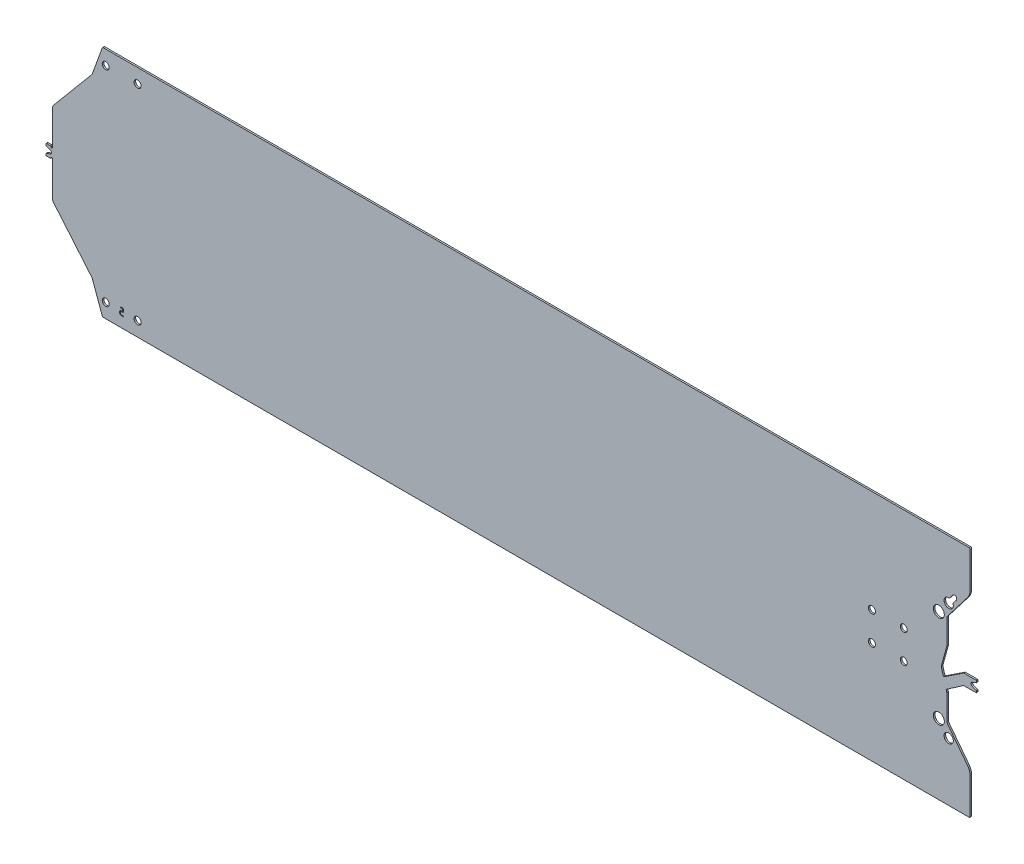
SolidWorks part; units mm, degrees
extrude "Base-Extrude" add sketch "Sketch1" along normal blind 5
sketch "Sketch1" plane through (0, 0, 0) normal (0, 0, 1) x (1, 0, 0)
  line L0 (0, 363.5) -> (0, 252.0782)
  line L1 (81.8142, 0) -> (-2880, 0) construction
  line L2 (-3, 366.5) -> (-2720.5358, 366.5)
  line L3 (-2754.7906, -278.1569) -> (-2723.3548, -364.5261)
  line L4 (-2756.5271, 275.1493) -> (-2875.3209, 133.5763)
  line L5 (-2880, 120.7206) -> (-2880, 0)
  line L6 (-2754.7906, 278.1569) -> (-2723.3548, 364.5261)
  line L7 (-2892.0623, 0) -> (-2897, 0)
  line L8 (-2900, -3) -> (-2900, -12.6577)
  line L9 (-2897.7276, -15.5681) -> (-2882.2724, -19.4319)
  line L10 (-2880, -1) -> (-2880, 0)
  line L11 (-2880, 90) -> (0, 90) construction
  line L12 (-2850.9687, 277.5) -> (0, 277.5) construction
  line L13 (-67, 90) -> (-67, 277.5) construction
  line L14 (-73, 63) -> (-89.7303, 2.6724)
  line L15 (-90.094, 0) -> (17, 0)
  line L16 (20, -3) -> (20, -17.4378)
  line L17 (-3, -366.5) -> (-2720.5358, -366.5)
  line L18 (-2880, -120.7206) -> (-2880, -22.3423)
  line L19 (0, -252.0782) -> (0, -363.5)
  line L20 (17.4693, -20.4008) -> (-80.5102, -35.9192)
  line L21 (-8.2659, 227.7277) -> (-70.9335, 146.0576)
  line L22 (-73, 139.97) -> (-73, 63)
  line L23 (-8.2659, -227.7277) -> (-70.9335, -146.0576)
  line L24 (-73, -63) -> (-73, -139.97)
  line L25 (-2756.5271, -275.1493) -> (-2875.3209, -133.5763)
  line L26 (-73, -63) -> (-80.5102, -35.9192)
  line L27 (-67, 183.75) -> (-48.7372, 207.5506) construction
  line L28 (-43.1837, 203.2893) -> (-52.7039, 190.8823)
  line L29 (-54.2906, 211.8119) -> (-63.8108, 199.405)
  circle A0 centre (-98, 145.25) radius 17.25
  arc A1 (-2723.3548, 364.5261) -> (-2720.5358, 366.5) centre (-2720.5358, 363.5) cw
  arc A2 (-2880, -120.7206) -> (-2875.3209, -133.5763) centre (-2860, -120.7206) ccw
  arc A3 (-2754.7906, -278.1569) -> (-2756.5271, -275.1493) centre (-2764.1876, -281.5771) ccw
  arc A4 (-2880, -1) -> (-2887.5832, -2.7778) centre (-2884, -1) cw
  arc A5 (-2887.5832, -2.7778) -> (-2892.0623, 0) centre (-2892.0623, -5) ccw
  arc A6 (-2723.3548, -364.5261) -> (-2720.5358, -366.5) centre (-2720.5358, -363.5) ccw
  arc A7 (-2754.7906, 278.1569) -> (-2756.5271, 275.1493) centre (-2764.1876, 281.5771) cw
  circle A8 centre (-2712.5, 321.5) radius 11
  circle A9 centre (-2612.5, 321.5) radius 11
  circle A10 centre (-2612.5, -321.5) radius 11
  circle A11 centre (-2712.5, -321.5) radius 11
  arc A12 (-43.1837, 203.2893) -> (-54.2906, 211.8119) centre (-48.7372, 207.5506) ccw
  arc A13 (-63.8108, 199.405) -> (-66.3296, 198.2345) centre (-66.1909, 201.2313) cw
  arc A14 (-2880, 120.7206) -> (-2875.3209, 133.5763) centre (-2860, 120.7206) cw
  arc A15 (0, 363.5) -> (-3, 366.5) centre (-3, 363.5) ccw
  arc A16 (0, 252.0782) -> (-8.2659, 227.7277) centre (-40, 252.0782) cw
  arc A17 (-73, 139.97) -> (-70.9335, 146.0576) centre (-63, 139.97) cw
  arc A18 (-52.7039, 190.8823) -> (-53.1826, 188.1464) centre (-50.3238, 189.0561) ccw
  arc A19 (-2900, -3) -> (-2897, 0) centre (-2897, -3) cw
  arc A20 (-2897.7276, -15.5681) -> (-2900, -12.6577) centre (-2897, -12.6577) cw
  arc A21 (-89.7303, 2.6724) -> (-90.094, 0) centre (-80.094, 0) ccw
  arc A22 (-73, -139.97) -> (-70.9335, -146.0576) centre (-63, -139.97) ccw
  arc A23 (0, -252.0782) -> (-8.2659, -227.7277) centre (-40, -252.0782) ccw
  arc A24 (-3, -366.5) -> (0, -363.5) centre (-3, -363.5) ccw
  arc A25 (-2882.2724, -19.4319) -> (-2880, -22.3423) centre (-2883, -22.3423) cw
  arc A26 (20, -3) -> (17, 0) centre (17, -3) ccw
  arc A27 (20, -17.4378) -> (17.4693, -20.4008) centre (17, -17.4378) cw
  circle A28 centre (-98, -145.25) radius 17.25
  arc A29 (-66.3296, 198.2345) -> (-53.1826, 188.1464) centre (-67, 183.75) ccw
  circle A30 centre (-67, -183.75) radius 14.5
  circle A31 centre (-308, 45) radius 11
  circle A32 centre (-208, 45) radius 11
  circle A33 centre (-308, -45) radius 11
  circle A34 centre (-208, -45) radius 11
  point P6 (-2722.6364, 366.5)
  point P45 (-2755.3937, 276.5)
  point P47 (-90.4714, 0)
  point P60 (-2880, 128)
  point P70 (0, 238.5)
  point P73 (-73, 143.3645)
  point P78 (-2900, 0)
  point P82 (-64.8232, 198.0857)
  point P85 (-73, -143.3645)
  point P88 (0, -238.5)
  point P92 (-2900, -15)
  point P95 (-2880, -20)
  point P100 (20, -20)
  point P112 (-53.7162, 189.563)
  dimension "D1" = 5
  dimension "D2" = 4
  dimension "D9" = 37.5
  dimension "D10" = 10
  dimension "D11" = 98
  dimension "D12" = 40
  dimension "D27" = 22
  dimension "D28" = 100
  dimension "D35" = 3
  dimension "D42" = 67
  dimension "D43" = 182.75
  dimension "D44" = 22
  dimension "D45" = 100
  dimension "D46" = 135
  dimension "D47" = 90
  dimension "D30" = 10
  dimension "D31" = 9
  dimension "D22" = 73
  dimension "D29" = 3
  dimension "D34" = 3
  dimension "D37" = 167.5
  dimension "D18" = 40
  dimension "D7" = 34.5
  dimension "D23" = 20
  dimension "D15" = 3
  dimension "D41" = 29
  dimension "D49" = 3
  dimension "D40" = 7
  dimension "D50" = 10
  dimension "D3" = 20
  dimension "D4" = 15
  dimension "D5" = 20
  dimension "D6" = 5
  dimension "D8" = 40
  dimension "D13" = 90
  dimension "D14" = 20
  dimension "D16" = 38.5
  dimension "D17" = 39
  dimension "D19" = 20
  dimension "D20" = 128
  dimension "D21" = 90
  dimension "D24" = 89
  dimension "D25" = 187.5
  dimension "D26" = 733
  dimension "D32" = 45
  dimension "D33" = 20
  dimension "D36" = 2880
  dimension "D38" = 30
  dimension "D39" = 27
  dimension "D48" = 15.5
bend "FlatBend2" bend angle 65 parameters "D1"=0, "D5"=2
bend "FlatBend1" bend angle 65 parameters "D1"=0, "D5"=1
bend "FlatBend5" bend angle 65 parameters "D1"=0, "D5"=5
bend "FlatBend4" bend angle 65 parameters "D1"=0, "D5"=4, "RD1"=249.3301, "RD2"=5
ref_plane "Front" through (0, 0, 0) normal (0, 0, 1) x (1, 0, 0)
ref_plane "Top" through (0, 0, 0) normal (0, 1, 0) x (1, 0, 0)
ref_plane "Right" through (0, 0, 0) normal (1, 0, 0) x (0, 0, -1)
sheet metal parameters "Sheet-Metal1" parameters "D1"=16
sketch "Sketch5" plane through (0, 0, 5) normal (0, 0, 1) x (1, 0, 0)
  line L0 (-2662.5, -310.5) -> (-2662.5, -326.75) construction
  line L1 (-2665.75, -313) -> (-2660.25, -313)
  line L2 (-2659.25, -314) -> (-2659.25, -319)
  line L3 (-2660.25, -320) -> (-2662.5, -320)
  line L4 (-2662.5, -333.5) -> (-2657.75, -333.5)
  line L5 (-2665.75, -310.5) -> (-2660.25, -310.5)
  line L6 (-2656.75, -314) -> (-2656.75, -319)
  line L7 (-2660.25, -322.5) -> (-2662.5, -322.5)
  line L8 (-2662.5, -331) -> (-2657.75, -331)
  line L9 (-2666.75, -311.5) -> (-2666.75, -312)
  line L10 (-2656.75, -332) -> (-2656.75, -332.5)
  line L11 (-2712.5, -310.5) -> (-2612.5, -310.5) construction
  line L12 (-2670.25, -310.5) -> (-2660.25, -310.5) construction
  line L13 (-2670.25, -313) -> (-2660.25, -313) construction
  line L14 (-2662.5, -331) -> (-2655.25, -331) construction
  line L15 (-2662.5, -333.5) -> (-2655.25, -333.5) construction
  arc A0 (-2662.5, -320) -> (-2662.5, -333.5) centre (-2662.5, -326.75) ccw
  arc A1 (-2660.25, -313) -> (-2659.25, -314) centre (-2660.25, -314) cw
  arc A2 (-2659.25, -319) -> (-2660.25, -320) centre (-2660.25, -319) cw
  arc A3 (-2660.25, -310.5) -> (-2656.75, -314) centre (-2660.25, -314) cw
  arc A4 (-2656.75, -319) -> (-2660.25, -322.5) centre (-2660.25, -319) cw
  arc A5 (-2662.5, -322.5) -> (-2662.5, -331) centre (-2662.5, -326.75) ccw
  circle A6 centre (-2712.5, -321.5) radius 11 construction
  circle A7 centre (-2612.5, -321.5) radius 11 construction
  arc A8 (-2665.75, -310.5) -> (-2666.75, -311.5) centre (-2665.75, -311.5) ccw
  arc A9 (-2665.75, -313) -> (-2666.75, -312) centre (-2665.75, -312) cw
  arc A10 (-2657.75, -331) -> (-2656.75, -332) centre (-2657.75, -332) cw
  arc A11 (-2657.75, -333.5) -> (-2656.75, -332.5) centre (-2657.75, -332.5) ccw
  dimension "D1" = 1
  dimension "D6" = 1
  dimension "D2" = 2.5
  dimension "D3" = 10
  dimension "D4" = 23
  dimension "D5" = 12
extrude "5 tal" cut sketch "Sketch5" against normal through all
flatten bends "Flatten-Bends1" parameters "D1"=8
sketch "Sharp-Sketch1" plane through (0, 0, 5) normal (0, 0, 1) x (1, 0, 0)
sketch "Sketch2" plane through (0, 0, 5) normal (0, 0, 1) x (1, 0, 0)
  line L0 (0, -524.6437) -> (-2880, -524.6437)
  line L1 (0, 479.3597) -> (0, 139.97)
  line L2 (-2880, 479.3597) -> (0, 479.3597)
  line L3 (-2880, 479.3597) -> (-2880, -524.6437)
  line L4 (-73, 139.97) -> (-73, 63) construction
  line L5 (-73, 63) -> (-89.7303, 2.6724) construction
  line L6 (-3, -366.5) -> (-2720.5358, -366.5) construction
  line L7 (-3, 366.5) -> (-2720.5358, 366.5) construction
  line L8 (-73, 139.97) -> (-73, 63)
  line L9 (690.6763, 0) -> (-641.7821, 0) construction
  line L10 (-73, -139.97) -> (0, -139.97)
  line L11 (0, -139.97) -> (0, -524.6437)
  line L12 (-73, 139.97) -> (0, 139.97)
  line L13 (-2880, 120.7206) -> (-2880, 0) construction
  line L15 (-73, 63) -> (-89.7303, 2.6724)
  line L16 (-73, -63) -> (-80.5102, -35.9192) construction
  line L17 (-73, -63) -> (-73, -139.97)
  line L18 (-73, -63) -> (-89.7303, -2.6724)
  arc A0 (-89.7303, 2.6724) -> (-90.094, 0) centre (-80.094, 0) ccw construction
  arc A1 (-89.7303, 2.6724) -> (-89.7303, -2.6724) centre (-80.094, 0) ccw
  dimension "D1" = 158.1437
  dimension "D2" = 112.8597
extrude "Bortskæring af bukkestop" cut sketch "Sketch2" against normal blind 5 flip side to cut
process bends "Process-Bends1" [suppressed]
sketch "Flat-Sketch1" plane through (0, 0, 5) normal (0, 0, 1) x (1, 0, 0)
  line L0 (-2850.9687, 277.5) -> (0, 277.5) construction
  line L1 (-2880, 90) -> (0, 90) construction
  line L2 (-2880, -120.7206) -> (-2880, 120.7206) construction
  line L11 (81.8142, 0) -> (-2880, 0) construction
  line L12 (-2850.9687, 277.5) -> (76.9875, 277.5) construction
  line L13 (-2880, 90) -> (0, 90) construction
  line L14 (81.8142, 0) -> (-2905, 0) construction
  line L15 (-2880, -90) -> (0, -90) construction
  line L16 (-2850.9687, -277.5) -> (76.9875, -277.5) construction
  point P10 (-1165, -293)
  point P11 (-1476.5, 183.75)
bend "FlatBend3" bend angle 50 parameters "D1"=0, "D5"=3
sketch "Tværsnitsmål" [suppressed] plane through (0, 0, 0) normal (1, 0, 0) x (0, 0, -1)
  line L2 (-159.2587, 285.6445) -> (-91.5524, 317.2165) construction
  line L3 (-80.4088, 317.2165) -> (-12.7024, 285.6445) construction
  line L4 (-76.683, 50.0209) -> (-12.7024, 79.8555) construction
  line L5 (-76.683, 50.0209) -> (-12.7024, 79.8555)
  line L6 (0, 265.7057) -> (0, 130.7882) construction
  line L7 (0, 265.7057) -> (0, 130.7882)
  line L8 (-159.2587, 79.8555) -> (-95.2782, 50.0209) construction
  line L9 (-159.2587, 79.8555) -> (-95.2782, 50.0209)
  line L10 (-171.9611, 226.4777) -> (-171.9611, 144.8076) construction
  line L11 (-171.9611, 226.4777) -> (-171.9611, 144.8076)
  point P0 (-85.9806, 319.8147)
  dimension "D1" = 248.4455
  dimension "D2" = 50
  dimension "D3" = 65
  dimension "D4" = 171.9611
sketch "Bukkelinier" plane through (0, 0, 0) normal (0, 0, -1) x (-1, 0, 0)
  line L0 (2850.9687, 277.5) -> (-76.9875, 277.5) construction
  line L1 (2880, 90) -> (0, 90) construction
  line L2 (-81.8142, 0) -> (2905, 0) construction
  line L3 (2880, -90) -> (0, -90) construction
  line L4 (2850.9687, -277.5) -> (-76.9875, -277.5) construction
  line L5 (2754.5546, 277.5) -> (0, 277.5) construction
  line L6 (2880, 90) -> (73, 90) construction
  line L7 (0, 0) -> (2905, 0) construction
  line L8 (2880, -90) -> (73, -90) construction
  line L9 (2754.5546, -277.5) -> (0, -277.5) construction
  line L10 (2756.5271, 275.1493) -> (2875.3209, 133.5763) construction
  line L11 (2756.5271, -275.1493) -> (2875.3209, -133.5763) construction
  line L12 (0, 363.5) -> (0, 252.0782) construction
  line L14 (0, -252.0782) -> (0, -363.5) construction
  line L15 (73, 139.97) -> (73, 63) construction
sketch "Sketch4" [suppressed] plane through (0, 0, 0) normal (0, 1, 0) x (1, 0, 0)
  line L0 (-2880, -85.9627) -> (0, -85.9627)
  line L1 (-2880, -77.0877) -> (-2880, -94.8377) construction
split line "Split Line1" [suppressed]
ref_plane "Symmetriplan" [suppressed] through (0, 0, 85.9627) normal (0, 0, 1) x (1, 0, 0)
ref_plane "Horisontalt plan - overside" [suppressed] through (0, 49.0631, 0) normal (0, 1, 0) x (-1, 0, 0)
sketch "Sketch6" plane through (0, 0, 5) normal (0, 0, 1) x (1, 0, 0)
  line L0 (0, 0) -> (-2905, 0) construction
  line L1 (0, 0) -> (-2891.2366, 0) construction
  line L2 (-2886.9479, 5.6382) -> (-2899.342, 10.1493)
  line L3 (-2900, 11.0889) -> (-2900, 16)
  line L4 (-2899, 17) -> (-2886, 17)
  line L5 (-2884, 15) -> (-2884, 14.5)
  line L6 (-2880, -120.7206) -> (-2880, 120.7206) construction
  line L7 (-2880, 14.5) -> (-2880, -14.5)
  line L8 (-2884, -15) -> (-2884, -14.5)
  line L9 (-2899, -17) -> (-2886, -17)
  line L10 (-2900, -11.0889) -> (-2900, -16)
  line L11 (-2886.9479, -5.6382) -> (-2899.342, -10.1493)
  line L12 (6.9479, 5.6382) -> (19.342, 10.1493)
  line L13 (20, 11.0889) -> (20, 16)
  line L14 (19, 17) -> (-19.0981, 17)
  line L15 (19, -17) -> (-19.0675, -17)
  line L16 (20, -11.0889) -> (20, -16)
  line L17 (6.9479, -5.6382) -> (19.342, -10.1493)
  line L18 (0, 363.5) -> (0, 252.0782) construction
  line L19 (-75.2186, -55) -> (-20.7682, -17.5287)
  line L20 (-73, -63) -> (-89.7303, -2.6724) construction
  line L21 (-20.7524, 16.5027) -> (-83.5383, -25)
  line L22 (-75.2186, -55) -> (-83.5383, -25)
  line L23 (-2880, -90) -> (-73, -90) construction
  arc A0 (-2886.9479, 5.6382) -> (-2886.9479, -5.6382) centre (-2889, 0) cw
  arc A1 (-2884, 14.5) -> (-2880, 14.5) centre (-2882, 14.5) ccw
  arc A2 (-2884, -14.5) -> (-2880, -14.5) centre (-2882, -14.5) cw
  arc A3 (-2886, 17) -> (-2884, 15) centre (-2886, 15) cw
  arc A4 (-2884, -15) -> (-2886, -17) centre (-2886, -15) cw
  arc A5 (-2900, 16) -> (-2899, 17) centre (-2899, 16) cw
  arc A6 (-2899.342, 10.1493) -> (-2900, 11.0889) centre (-2899, 11.0889) cw
  arc A7 (-2900, -11.0889) -> (-2899.342, -10.1493) centre (-2899, -11.0889) cw
  arc A8 (-2899, -17) -> (-2900, -16) centre (-2899, -16) cw
  arc A9 (6.9479, 5.6382) -> (6.9479, -5.6382) centre (9, 0) ccw
  arc A10 (-19.0981, 17) -> (-20.7524, 16.5027) centre (-19.0981, 14) ccw
  arc A11 (-19.0675, -17) -> (-20.7682, -17.5287) centre (-19.0675, -20) ccw
  arc A12 (20, 16) -> (19, 17) centre (19, 16) ccw
  arc A13 (19.342, 10.1493) -> (20, 11.0889) centre (19, 11.0889) ccw
  arc A14 (20, -11.0889) -> (19.342, -10.1493) centre (19, -11.0889) ccw
  arc A15 (19, -17) -> (20, -16) centre (19, -16) ccw
  point P2 (-2880, 0)
  point P23 (-2884, 17)
  point P26 (-2884, -17)
  point P29 (-2900, 17)
  point P32 (-2900, 10.3887)
  point P35 (-2900, -10.3887)
  point P38 (-2900, -17)
  point P58 (-20, 17)
  point P61 (-20, -17)
  point P64 (20, 17)
  point P67 (20, 10.3887)
  point P70 (20, -10.3887)
  point P73 (20, -17)
  dimension "D1" = 6
  dimension "D4" = 2
  dimension "D8" = 2
  dimension "D9" = 1
  dimension "D10" = 6
  dimension "D18" = 3
  dimension "D19" = 1
  dimension "D2" = 20
  dimension "D3" = 40
  dimension "D5" = 29
  dimension "D6" = 34
  dimension "D7" = 11
  dimension "D11" = 40
  dimension "D12" = 11
  dimension "D13" = 20
  dimension "D14" = 34
  dimension "D15" = 40
  dimension "D16" = 35
  dimension "D17" = 30
extrude "Farina bukkestops" add sketch "Sketch6" against normal blind 5
